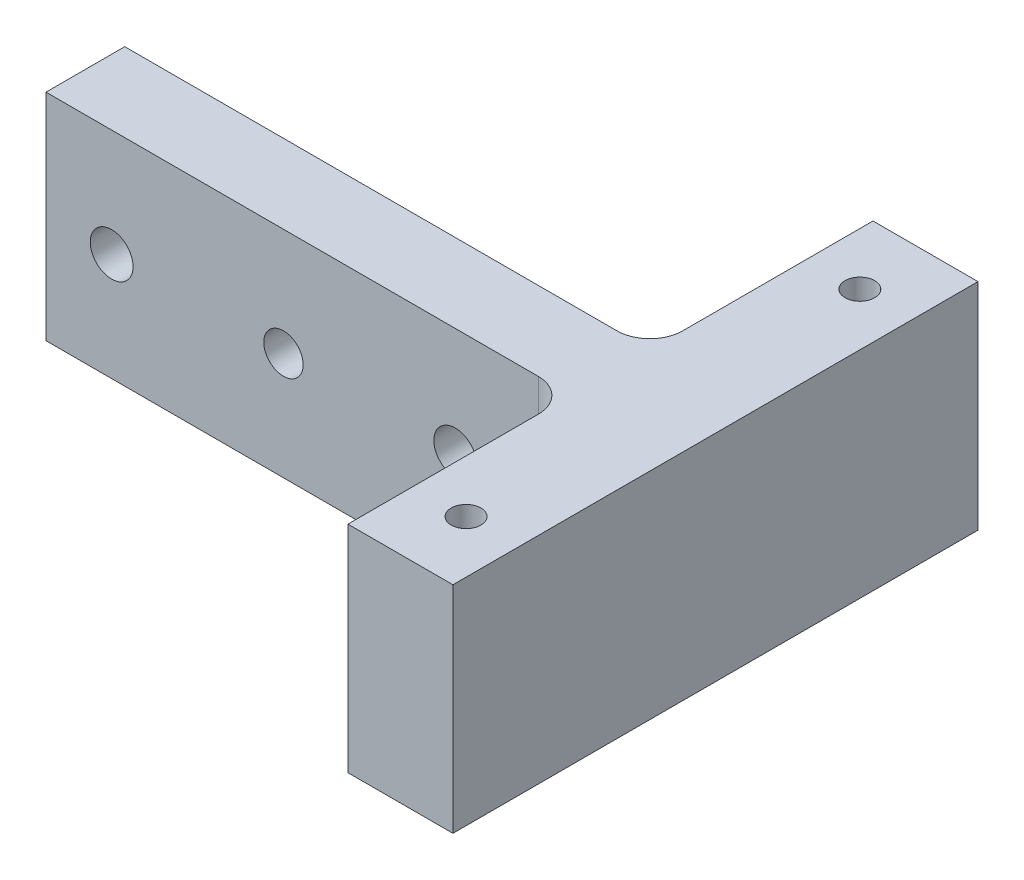
SolidWorks part; units mm, degrees
ref_plane "Front Plane" through (0, 0, 0) normal (0, 0, 1) x (1, 0, 0)
ref_plane "Top Plane" through (0, 0, 0) normal (0, 1, 0) x (1, 0, 0)
ref_plane "Right Plane" through (0, 0, 0) normal (1, 0, 0) x (0, 0, -1)
sketch "Sketch1" plane through (0, 0, 0) normal (0, 1, 0) x (1, 0, 0)
  line L0 (-4, -3) -> (-4, -20)
  line L1 (-4, 20) -> (4, 20)
  line L2 (-4, 20) -> (-4, 3)
  line L3 (-4, -20) -> (4, -20)
  line L4 (4, 20) -> (4, -20)
  line L5 (-4, 20) -> (4, -20) construction
  line L6 (-4, -20) -> (4, 20) construction
  line L7 (-4, -3) -> (-44, -3)
  line L9 (-4, 3) -> (-44, 3)
  line L10 (-44, -3) -> (-44, 3)
  point P0 (0, 0)
  point P10 (-44, 0)
  dimension "D1" = 8
  dimension "D2" = 40
  dimension "D3" = 40
  dimension "D4" = 6
extrude "Boss-Extrude1" add sketch "Sketch1" along normal blind 16.4
hole_wizard "#4-40 Tapped Hole1" positions "Sketch4" profile "Sketch5" tap size "#4-40" standard "ANSI Inch" end condition through all
sketch "Sketch4" plane through (0, 16.4, 0) normal (0, 1, 0) x (1, 0, 0)
  line L1 (-4, -20) -> (4, -20) construction
  line L2 (4, 20) -> (-4, 20) construction
  point P0 (0, 15)
  point P2 (0, -15)
  dimension "D1" = 5
  dimension "D2" = 5
sketch "Sketch5" plane through (0, 16.4, -15) normal (1, 0, 0) x (0, 0, 1)
  line L0 (0, 0) -> (0, 16.4)
  line L1 (0, 16.4) -> (1.1303, 16.4)
  line L2 (1.1303, 16.4) -> (1.1303, 0)
  line L5 (1.1303, 0) -> (0, 0)
  line L11 (0, -6.35) -> (0, 107.95) construction
  dimension "Thru Tap Drill Dia." = 2.2606
  dimension "Thru Tap Drill Depth" = 16.4
cosmetic thread "Hole Thread1"
cosmetic thread "Hole Thread2"
hole_wizard "Ø3.0mm Dowel Hole1" positions "Sketch6" profile "Sketch7" hole size "Ø3.0" standard "ANSI Metric" end condition through all
sketch "Sketch6" plane through (0, 0, 3) normal (0, 0, 1) x (1, 0, 0)
  line L0 (-44, 16.4) -> (-44, 0) construction
  line L1 (-44, 0) -> (-4, 0) construction
  point P0 (-25.91, 8.2)
  dimension "D1" = 18.09
  dimension "D2" = 8.2
sketch "Sketch7" plane through (-25.91, 8.2, 3) normal (1, 0, 0) x (0, -1, 0)
  line L0 (0, 0) -> (0, 23)
  line L1 (0, 23) -> (1.5, 23)
  line L2 (1.5, 23) -> (1.5, 0)
  line L5 (1.5, 0) -> (0, 0)
  line L11 (0, -6.35) -> (0, 107.95) construction
  dimension "Thru Hole Dia." = 3
  dimension "Thru Hole Depth" = 23
hole_wizard "#4 Clearance Hole1" positions "Sketch8" profile "Sketch9" hole size "#4" standard "ANSI Inch" end condition through all
sketch "Sketch8" plane through (0, 0, 3) normal (0, 0, 1) x (1, 0, 0)
  line L0 (-44, 16.4) -> (-44, 0) construction
  line L1 (-44, 0) -> (-4, 0) construction
  point P0 (-39, 8.2)
  point P2 (-12.82, 8.2)
  dimension "D1" = 5
  dimension "D2" = 26.18
  dimension "D3" = 8.2
sketch "Sketch9" plane through (-39, 8.2, 3) normal (1, 0, 0) x (0, -1, 0)
  line L0 (0, 0) -> (0, 23)
  line L1 (0, 23) -> (1.6319, 23)
  line L2 (1.6319, 23) -> (1.6319, 0)
  line L5 (1.6319, 0) -> (0, 0)
  line L11 (0, -6.35) -> (0, 107.95) construction
  dimension "Thru Hole Dia." = 3.2639
  dimension "Thru Hole Depth" = 23
fillet "Fillet1" radius 2.5 2 edges at (-4, 8.2, -3) (-4, 8.2, 3)
equation "\"D2@Sketch4\"=\"D1@Sketch4\""
